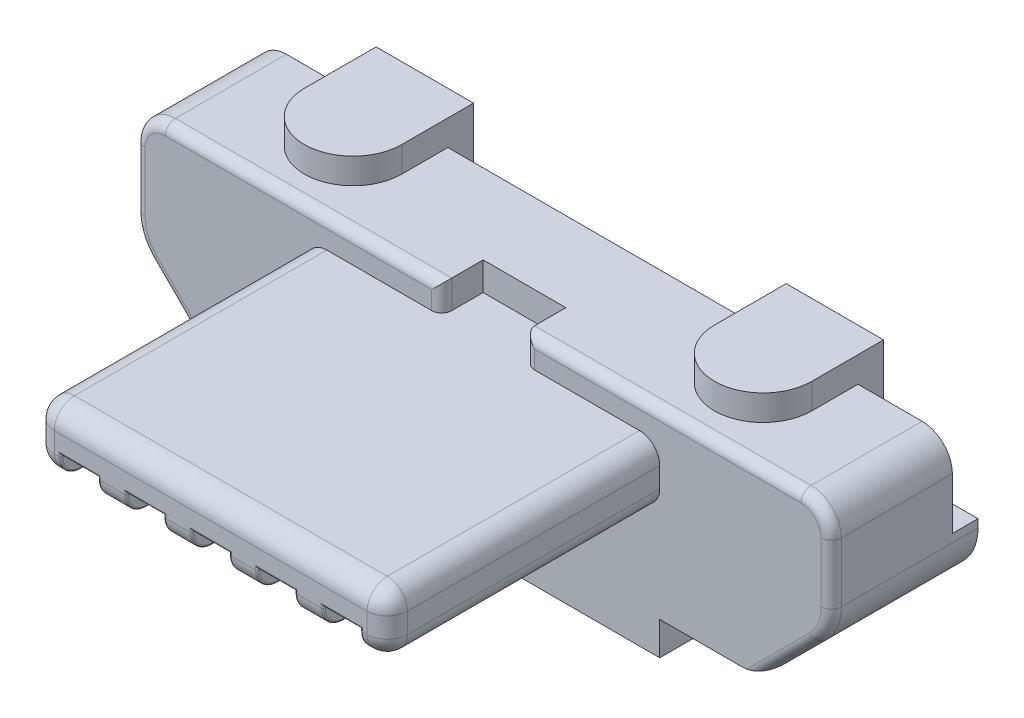
SolidWorks part; units mm, degrees
ref_plane "Front Plane" through (0, 0, 0) normal (0, 0, 1) x (1, 0, 0)
ref_plane "Top Plane" through (0, 0, 0) normal (0, 1, 0) x (1, 0, 0)
ref_plane "Right Plane" through (0, 0, 0) normal (1, 0, 0) x (0, 0, -1)
sketch "Sketch1" plane through (0, 0, 0) normal (0, 0, 1) x (1, 0, 0)
  line L0 (3.45, 0.925) -> (-3.45, 0.925)
  line L1 (-3.45, 0.925) -> (-3.45, -0.175)
  line L2 (-3.45, -0.175) -> (-2.7, -0.925)
  line L3 (-2.7, -0.925) -> (2.7, -0.925)
  line L4 (2.7, -0.925) -> (3.45, -0.175)
  line L5 (3.45, -0.175) -> (3.45, 0.925)
  line L6 (0, 0.925) -> (0, -0.925) construction
  dimension "D1" = 6.9
  dimension "D2" = 1.85
extrude "Boss-Extrude1" add sketch "Sketch1" along normal blind 1.2
fillet "Fillet1" radius 0.3 2 edges at (-3.45, 0.925, 0.6) (3.45, 0.925, 0.6)
sketch "Sketch5" plane through (0, -0.925, 0) normal (0, -1, 0) x (1, 0, 0)
  line L0 (-2.7, 1.2) -> (2.7, 1.2) construction
  line L1 (-1.75, 1.2) -> (1.75, 1.2)
  line L2 (-1.75, 1.2) -> (-1.75, 0.8)
  line L3 (-1.75, 0.8) -> (1.75, 0.8)
  line L4 (1.75, 1.2) -> (1.75, 0.8)
  line L5 (0, 0.8) -> (0, 0) construction
  dimension "D1" = 0.4
  dimension "D2" = 3.5
extrude "Boss-Extrude3" add sketch "Sketch5" along normal blind 0.28
sketch "Sketch7" plane through (-1.75, 0, 0) normal (-1, 0, 0) x (0, 0, 1)
  line L0 (0, -0.925) -> (1.2, -0.875)
  line L1 (1.2, -0.925) -> (0, -0.925)
  line L2 (1.2, -0.925) -> (1.2, -0.875)
  dimension "D1" = 0.05
extrude "Cut-Extrude3" cut sketch "Sketch7" along normal blind 2.28
sketch "Sketch8" plane through (1.75, 0, 0) normal (1, 0, 0) x (0, 0, -1)
  line L3 (0, -0.925) -> (-1.2, -0.875)
  line L4 (-1.2, -0.875) -> (-1.2, -0.925)
  line L5 (-1.2, -0.925) -> (0, -0.925)
  line L6 (0, -0.925) -> (-1.2, -0.875)
  line L7 (-1.2, -0.875) -> (-1.2, -0.925)
  line L8 (-1.2, -0.925) -> (0, -0.925)
  dimension "D1" = 0
extrude "Cut-Extrude4" cut sketch "Sketch8" along normal blind 2.28
sketch "Sketch2" plane through (0, 0, 1.2) normal (0, 0, 1) x (1, 0, 0)
  line L1 (-0.41, 1.465) -> (0.41, 1.465)
  line L2 (-0.41, 1.465) -> (-0.41, 0.645)
  line L3 (-0.41, 0.645) -> (0.41, 0.645)
  line L4 (0.41, 1.465) -> (0.41, 0.645)
  line L5 (-0.41, 1.465) -> (0.41, 0.645) construction
  line L6 (-0.41, 0.645) -> (0.41, 1.465) construction
  line L7 (3.15, 0.925) -> (-3.15, 0.925) construction
  point P0 (0, 1.055)
  dimension "D1" = 0.82
  dimension "D2" = 0.28
extrude "Cut-Extrude1" cut sketch "Sketch2" against normal blind 0.41
sketch "Sketch3" plane through (0, 0, 1.2) normal (0, 0, 1) x (1, 0, 0)
  line L1 (-1.75, 0.645) -> (1.75, 0.645)
  line L2 (-1.75, 0.645) -> (-1.75, 0.045)
  line L3 (-1.75, 0.045) -> (1.75, 0.045)
  line L4 (1.75, 0.645) -> (1.75, 0.045)
  line L5 (-1.75, 0.645) -> (1.75, 0.045) construction
  line L6 (-1.75, 0.045) -> (1.75, 0.645) construction
  line L7 (3.15, 0.925) -> (0.41, 0.925) construction
  point P0 (0, 0.345)
  dimension "D1" = 0.28
  dimension "D2" = 3.5
  dimension "D3" = 0.6
extrude "Boss-Extrude2" add sketch "Sketch3" along normal blind 2.7
fillet "Fillet5" radius 0.2 8 edges at (0, 0.045, 3.9) (-1.75, 0.345, 3.9) (0, 0.645, 3.9) (1.75, 0.345, 3.9) (-1.75, 0.045, 2.55) (-1.75, 0.645, 2.55) (1.75, 0.045, 2.55) (1.75, 0.645, 2.55)
fillet "Fillet7" radius 0.5 4 edges at (3.45, -0.175, 0.6) (2.725, -0.9, 0.6) (-2.725, -0.9, 0.6) (-3.45, -0.175, 0.6)
fillet "Fillet8" radius 0.1 12 edges at (-3.45, 0.3286, 1.2) (3.45, 0.3286, 1.2) (3.3621, 0.8371, 1.2) (-3.3621, 0.8371, 1.2) (-1.78, 0.925, 1.2) (1.78, 0.925, 1.2) (3.1002, -0.5248, 1.2) (-3.1002, -0.5248, 1.2) (3.4119, -0.1592, 1.2) (-3.4119, -0.1592, 1.2)
sketch "Sketch9" plane through (0, -0.925, 0) normal (0, -1, 0) x (1, 0, 0)
  line L0 (1.75, 0.8) -> (1.75, 0) construction
  line L1 (-1.75, 0.05) -> (1.75, 0.05)
  line L2 (-1.75, 0.05) -> (-1.75, 0.65)
  line L3 (-1.75, 0.65) -> (1.75, 0.65)
  line L4 (1.75, 0.05) -> (1.75, 0.65)
  line L5 (-1.75, 0) -> (1.75, 0) construction
  dimension "D1" = 0.05
  dimension "D2" = 0.6
extrude "Boss-Extrude4" add sketch "Sketch9" along normal blind 0.16
sketch "Sketch10" plane through (0, 0, 3.9) normal (0, 0, 1) x (1, 0, 0)
  line L0 (-1.3, 0.265) -> (-1.3, -0.105) construction
  line L1 (-1.485, 0.265) -> (-1.115, 0.265)
  line L2 (-1.485, 0.265) -> (-1.485, -0.105)
  line L3 (-1.485, -0.105) -> (-1.115, -0.105)
  line L4 (-1.115, 0.265) -> (-1.115, -0.105)
  line L5 (-0.835, 0.265) -> (-0.465, 0.265)
  line L6 (-0.835, 0.265) -> (-0.835, -0.105)
  line L7 (-0.835, -0.105) -> (-0.465, -0.105)
  line L8 (-0.465, 0.265) -> (-0.465, -0.105)
  line L9 (-0.185, 0.265) -> (0.185, 0.265)
  line L10 (-0.185, 0.265) -> (-0.185, -0.105)
  line L11 (-0.185, -0.105) -> (0.185, -0.105)
  line L12 (0.185, 0.265) -> (0.185, -0.105)
  line L13 (0.465, 0.265) -> (0.835, 0.265)
  line L14 (0.465, 0.265) -> (0.465, -0.105)
  line L15 (0.465, -0.105) -> (0.835, -0.105)
  line L16 (0.835, 0.265) -> (0.835, -0.105)
  line L17 (1.115, 0.265) -> (1.485, 0.265)
  line L18 (1.115, 0.265) -> (1.115, -0.105)
  line L19 (1.115, -0.105) -> (1.485, -0.105)
  line L20 (1.485, 0.265) -> (1.485, -0.105)
  line L21 (1.3, 0.265) -> (1.3, -0.105) construction
  line L22 (0.65, 0.265) -> (0.65, -0.105) construction
  line L23 (0, 0.265) -> (0, -0.105) construction
  line L24 (-0.65, 0.265) -> (-0.65, -0.105) construction
  line L25 (-1.55, 0.045) -> (1.55, 0.045) construction
  dimension "D1" = 0.37
  dimension "D2" = 2.6
  dimension "D3" = 0.28
  dimension "D4" = 0.28
  dimension "D5" = 0.28
  dimension "D6" = 0.28
  dimension "D7" = 0.22
extrude "Cut-Extrude5" cut sketch "Sketch10" against normal up to surface (2.7 mm away) up to face at (0.0371, 0.0086, 1.2)
ref_plane "Plane1" through (0, 0, 3.7) normal (0, 0, 1) x (1, 0, 0)
sketch "Sketch11" plane through (0, 0, 3.7) normal (0, 0, 1) x (1, 0, 0)
  line L0 (-1.485, 0.045) -> (-1.485, 0.265) construction
  line L1 (-1.485, 0.165) -> (-1.115, 0.165)
  line L2 (-1.485, 0.165) -> (-1.485, 0.315)
  line L3 (-1.485, 0.315) -> (-1.115, 0.315)
  line L4 (-1.115, 0.165) -> (-1.115, 0.315)
  line L5 (-0.51, 0.645) -> (-1.55, 0.645) construction
  line L6 (-1.115, 0.245) -> (-1.115, 0.045) construction
  line L7 (-0.835, 0.315) -> (-0.465, 0.315)
  line L8 (-0.835, 0.165) -> (-0.835, 0.315)
  line L9 (-0.835, 0.165) -> (-0.465, 0.165)
  line L10 (-0.465, 0.165) -> (-0.465, 0.315)
  line L11 (-0.185, 0.315) -> (0.185, 0.315)
  line L12 (-0.185, 0.165) -> (-0.185, 0.315)
  line L13 (-0.185, 0.165) -> (0.185, 0.165)
  line L14 (0.185, 0.165) -> (0.185, 0.315)
  line L15 (0.465, 0.315) -> (0.835, 0.315)
  line L16 (0.465, 0.165) -> (0.465, 0.315)
  line L17 (0.465, 0.165) -> (0.835, 0.165)
  line L18 (0.835, 0.165) -> (0.835, 0.315)
  line L19 (1.115, 0.315) -> (1.485, 0.315)
  line L20 (1.115, 0.165) -> (1.115, 0.315)
  line L21 (1.115, 0.165) -> (1.485, 0.165)
  line L22 (1.485, 0.165) -> (1.485, 0.315)
  dimension "D1" = 0.15
  dimension "D2" = 0.48
  dimension "D3" = 5
sketch "Sketch12" plane through (0, 0, 0) normal (1, 0, 0) x (0, 0, -1)
  line L0 (-3.7, 0.315) -> (-0.55, 0.315)
  line L1 (-3.7, 0.165) -> (-3.7, 0.315) construction
  line L2 (-3.7, 0.165) -> (-3.7, 0.315) construction
  line L3 (-0.35, 0.115) -> (-0.35, -1.085)
  line L4 (0, -0.7781) -> (0, -0.3214) construction
  line L5 (-0.05, -1.085) -> (-0.65, -1.085) construction
  arc A0 (-0.55, 0.315) -> (-0.35, 0.115) centre (-0.55, 0.115) cw
  dimension "D1" = 0.2
  dimension "D2" = 0.35
sketch "Sketch13" plane through (0, 0, 3.7) normal (0, 0, 1) x (1, 0, 0)
  line L0 (-1.485, 0.315) -> (-1.115, 0.315) construction
  line L1 (-1.425, 0.315) -> (-1.175, 0.315)
  line L2 (-1.425, 0.315) -> (-1.425, 0.165)
  line L3 (-1.425, 0.165) -> (-1.175, 0.165)
  line L4 (-1.175, 0.315) -> (-1.175, 0.165)
  line L5 (-1.485, 0.165) -> (-1.115, 0.165) construction
  line L6 (-1.485, 0.045) -> (-1.175, 0.315) construction
  line L7 (-1.175, 0.315) -> (-1.1728, 0.3168) construction
  line L8 (-1.115, 0.045) -> (-1.425, 0.315) construction
  line L12 (-0.775, 0.315) -> (-0.525, 0.315)
  line L13 (-0.775, 0.315) -> (-0.775, 0.165)
  line L14 (-0.775, 0.165) -> (-0.525, 0.165)
  line L15 (-0.525, 0.315) -> (-0.525, 0.165)
  line L16 (-0.125, 0.315) -> (0.125, 0.315)
  line L17 (-0.125, 0.315) -> (-0.125, 0.165)
  line L18 (-0.125, 0.165) -> (0.125, 0.165)
  line L19 (0.125, 0.315) -> (0.125, 0.165)
  line L20 (0.525, 0.315) -> (0.775, 0.315)
  line L21 (0.525, 0.315) -> (0.525, 0.165)
  line L22 (0.525, 0.165) -> (0.775, 0.165)
  line L23 (0.775, 0.315) -> (0.775, 0.165)
  line L24 (1.175, 0.315) -> (1.425, 0.315)
  line L25 (1.175, 0.315) -> (1.175, 0.165)
  line L26 (1.175, 0.165) -> (1.425, 0.165)
  line L27 (1.425, 0.315) -> (1.425, 0.165)
  dimension "D1" = 0.25
  dimension "D2" = 5
sweep "Cut-Sweep2" cut profiles "Sketch13" path "Sketch12"
extrude "Cut-Extrude6" cut sketch "Sketch11" against normal blind 2.8
sketch "Sketch14" plane through (0, 0, 3.7) normal (0, 0, 1) x (1, 0, 0)
  line L4 (-1.175, 0.315) -> (-1.425, 0.315)
  line L5 (-1.175, 0.165) -> (-1.175, 0.315)
  line L6 (-1.425, 0.165) -> (-1.175, 0.165)
  line L7 (-1.425, 0.315) -> (-1.425, 0.165)
  line L8 (-1.175, 0.315) -> (-1.425, 0.315)
  line L9 (-1.175, 0.165) -> (-1.175, 0.315)
  line L10 (-1.425, 0.165) -> (-1.175, 0.165)
  line L11 (-1.425, 0.315) -> (-1.425, 0.165)
  line L12 (1.425, 0.315) -> (1.175, 0.315)
  line L13 (1.425, 0.165) -> (1.425, 0.315)
  line L14 (1.175, 0.165) -> (1.425, 0.165)
  line L15 (1.175, 0.315) -> (1.175, 0.165)
  line L16 (1.425, 0.315) -> (1.175, 0.315)
  line L17 (1.425, 0.165) -> (1.425, 0.315)
  line L18 (1.175, 0.165) -> (1.425, 0.165)
  line L19 (1.175, 0.315) -> (1.175, 0.165)
  line L20 (0.775, 0.315) -> (0.525, 0.315)
  line L21 (0.775, 0.165) -> (0.775, 0.315)
  line L22 (0.525, 0.165) -> (0.775, 0.165)
  line L23 (0.525, 0.315) -> (0.525, 0.165)
  line L24 (0.775, 0.315) -> (0.525, 0.315)
  line L25 (0.775, 0.165) -> (0.775, 0.315)
  line L26 (0.525, 0.165) -> (0.775, 0.165)
  line L27 (0.525, 0.315) -> (0.525, 0.165)
  line L28 (0.125, 0.315) -> (-0.125, 0.315)
  line L29 (0.125, 0.165) -> (0.125, 0.315)
  line L30 (-0.125, 0.165) -> (0.125, 0.165)
  line L31 (-0.125, 0.315) -> (-0.125, 0.165)
  line L32 (0.125, 0.315) -> (-0.125, 0.315)
  line L33 (0.125, 0.165) -> (0.125, 0.315)
  line L34 (-0.125, 0.165) -> (0.125, 0.165)
  line L35 (-0.125, 0.315) -> (-0.125, 0.165)
  line L36 (-0.525, 0.315) -> (-0.775, 0.315)
  line L37 (-0.775, 0.315) -> (-0.775, 0.165)
  line L38 (-0.775, 0.165) -> (-0.525, 0.165)
  line L39 (-0.525, 0.165) -> (-0.525, 0.315)
  line L40 (-0.525, 0.315) -> (-0.775, 0.315)
  line L41 (-0.775, 0.315) -> (-0.775, 0.165)
  line L42 (-0.775, 0.165) -> (-0.525, 0.165)
  line L43 (-0.525, 0.165) -> (-0.525, 0.315)
  dimension "D1" = 0
  dimension "D2" = 0
  dimension "D3" = 0
  dimension "D4" = 0
  dimension "D5" = 0
sketch "Sketch15" plane through (0, 0, 0) normal (1, 0, 0) x (0, 0, -1)
  line L1 (0, -0.7781) -> (0, -0.3214) construction
  line L4 (-0.35, 0.115) -> (-0.35, -1.085) construction
  line L5 (-3.7, 0.315) -> (-0.55, 0.315) construction
  line L6 (-0.35, 0.115) -> (-0.35, -1.035)
  line L7 (-0.3, -1.085) -> (0.889, -1.085)
  line L9 (-0.05, -1.085) -> (-0.65, -1.085) construction
  line L10 (-3.7, 0.315) -> (-0.55, 0.315)
  arc A2 (-0.35, 0.115) -> (-0.55, 0.315) centre (-0.55, 0.115) ccw construction
  arc A4 (-0.35, -1.035) -> (-0.3, -1.085) centre (-0.3, -1.035) ccw
  arc A5 (-0.35, 0.115) -> (-0.55, 0.315) centre (-0.55, 0.115) ccw
  dimension "D1" = 0.889
  dimension "D2" = 0.05
sweep "Sweep3" add profiles "Sketch14" path "Sketch15"
sketch "Sketch16" plane through (0, -1.085, 0) normal (0, -1, 0) x (1, 0, 0)
  line L0 (1.75, 0.65) -> (-1.75, 0.65) construction
  line L1 (-1.175, 0.5) -> (-1.425, 0.5)
  line L2 (-1.175, 0.5) -> (-1.175, 0.65)
  line L3 (-1.175, 0.65) -> (-1.425, 0.65)
  line L4 (-1.425, 0.5) -> (-1.425, 0.65)
  line L5 (-1.425, 0.5) -> (-1.425, 0.3) construction
  line L6 (-0.775, 0.5) -> (-0.775, 0.65)
  line L7 (-0.525, 0.65) -> (-0.775, 0.65)
  line L8 (-0.525, 0.5) -> (-0.525, 0.65)
  line L9 (-0.525, 0.5) -> (-0.775, 0.5)
  line L10 (-0.125, 0.5) -> (-0.125, 0.65)
  line L11 (0.125, 0.65) -> (-0.125, 0.65)
  line L12 (0.125, 0.5) -> (0.125, 0.65)
  line L13 (0.125, 0.5) -> (-0.125, 0.5)
  line L14 (0.525, 0.5) -> (0.525, 0.65)
  line L15 (0.775, 0.65) -> (0.525, 0.65)
  line L16 (0.775, 0.5) -> (0.775, 0.65)
  line L17 (0.775, 0.5) -> (0.525, 0.5)
  line L18 (1.175, 0.5) -> (1.175, 0.65)
  line L19 (1.425, 0.65) -> (1.175, 0.65)
  line L20 (1.425, 0.5) -> (1.425, 0.65)
  line L21 (1.425, 0.5) -> (1.175, 0.5)
  dimension "D1" = 5
extrude "Cut-Extrude7" cut sketch "Sketch16" against normal up to surface (0.16 mm away) up to face at (0, -0.925, 0.725)
sketch "Sketch17" plane through (0, 0, 3.7) normal (0, 0, 1) x (1, 0, 0)
  line L4 (-0.465, 0.315) -> (-0.835, 0.315)
  line L5 (-0.465, 0.165) -> (-0.465, 0.315)
  line L6 (-0.835, 0.165) -> (-0.465, 0.165)
  line L7 (-0.835, 0.315) -> (-0.835, 0.165)
  line L8 (-0.465, 0.315) -> (-0.835, 0.315)
  line L9 (-0.465, 0.165) -> (-0.465, 0.315)
  line L10 (-0.835, 0.165) -> (-0.465, 0.165)
  line L11 (-0.835, 0.315) -> (-0.835, 0.165)
  line L12 (-1.485, 0.165) -> (-1.115, 0.165)
  line L13 (-1.115, 0.165) -> (-1.115, 0.315)
  line L14 (-1.115, 0.315) -> (-1.485, 0.315)
  line L15 (-1.485, 0.315) -> (-1.485, 0.165)
  line L16 (-1.485, 0.165) -> (-1.115, 0.165)
  line L17 (-1.115, 0.165) -> (-1.115, 0.315)
  line L18 (-1.115, 0.315) -> (-1.485, 0.315)
  line L19 (-1.485, 0.315) -> (-1.485, 0.165)
  line L20 (1.485, 0.315) -> (1.115, 0.315)
  line L21 (1.485, 0.165) -> (1.485, 0.315)
  line L22 (1.115, 0.165) -> (1.485, 0.165)
  line L23 (1.115, 0.315) -> (1.115, 0.165)
  line L24 (1.485, 0.315) -> (1.115, 0.315)
  line L25 (1.485, 0.165) -> (1.485, 0.315)
  line L26 (1.115, 0.165) -> (1.485, 0.165)
  line L27 (1.115, 0.315) -> (1.115, 0.165)
  line L28 (0.835, 0.315) -> (0.465, 0.315)
  line L29 (0.835, 0.165) -> (0.835, 0.315)
  line L30 (0.465, 0.165) -> (0.835, 0.165)
  line L31 (0.465, 0.315) -> (0.465, 0.165)
  line L32 (0.835, 0.315) -> (0.465, 0.315)
  line L33 (0.835, 0.165) -> (0.835, 0.315)
  line L34 (0.465, 0.165) -> (0.835, 0.165)
  line L35 (0.465, 0.315) -> (0.465, 0.165)
  line L36 (0.185, 0.315) -> (-0.185, 0.315)
  line L37 (0.185, 0.165) -> (0.185, 0.315)
  line L38 (-0.185, 0.165) -> (0.185, 0.165)
  line L39 (-0.185, 0.315) -> (-0.185, 0.165)
  line L40 (0.185, 0.315) -> (-0.185, 0.315)
  line L41 (0.185, 0.165) -> (0.185, 0.315)
  line L42 (-0.185, 0.165) -> (0.185, 0.165)
  line L43 (-0.185, 0.315) -> (-0.185, 0.165)
  dimension "D1" = 0
  dimension "D2" = 0
  dimension "D3" = 0
  dimension "D4" = 0
  dimension "D5" = 0
extrude "Boss-Extrude5" add sketch "Sketch17" against normal blind 2.8
sketch "Sketch18" plane through (0, 0.315, 0) normal (0, -1, 0) x (1, 0, 0)
  line L0 (0.11, 3.7) -> (-0.11, 3.7) construction
  line L1 (1.115, 3.7) -> (1.485, 3.7)
  line L2 (1.115, 3.7) -> (1.115, 3.55)
  line L3 (1.115, 3.55) -> (1.485, 3.55)
  line L4 (1.485, 3.7) -> (1.485, 3.55)
  line L5 (1.115, 1.2) -> (1.115, 3.7) construction
  line L6 (1.485, 3.7) -> (1.485, 1.2) construction
  line L7 (0.465, 3.7) -> (0.835, 3.7)
  line L8 (0.465, 3.55) -> (0.835, 3.55)
  line L9 (0.465, 3.7) -> (0.465, 3.55)
  line L10 (0.835, 3.7) -> (0.835, 3.55)
  line L11 (-0.185, 3.7) -> (0.185, 3.7)
  line L12 (-0.185, 3.55) -> (0.185, 3.55)
  line L13 (-0.185, 3.7) -> (-0.185, 3.55)
  line L14 (0.185, 3.7) -> (0.185, 3.55)
  line L15 (-0.835, 3.7) -> (-0.465, 3.7)
  line L16 (-0.835, 3.55) -> (-0.465, 3.55)
  line L17 (-0.835, 3.7) -> (-0.835, 3.55)
  line L18 (-0.465, 3.7) -> (-0.465, 3.55)
  line L19 (-1.485, 3.7) -> (-1.115, 3.7)
  line L20 (-1.485, 3.55) -> (-1.115, 3.55)
  line L21 (-1.485, 3.7) -> (-1.485, 3.55)
  line L22 (-1.115, 3.7) -> (-1.115, 3.55)
  line L23 (-1.485, 0.9) -> (-1.485, 3.7) construction
  dimension "D1" = 0.15
  dimension "D2" = 5
extrude "Cut-Extrude8" cut sketch "Sketch18" against normal blind 0.15
fillet "Fillet10" radius 0.1 10 edges at (1.3, 0.315, 3.55) (0.65, 0.315, 3.55) (0, 0.315, 3.55) (-0.65, 0.315, 3.55) (-1.3, 0.315, 3.55) (-1.3, -1.085, 0.35) (-0.65, -1.085, 0.35) (0, -1.085, 0.35) (0.65, -1.085, 0.35) (1.3, -1.085, 0.35)
sketch "Sketch19" plane through (0, 0.315, 0) normal (0, 1, 0) x (1, 0, 0)
  line L0 (-0.11, -3.7) -> (0.11, -3.7) construction
  line L1 (-1.485, -3.7) -> (-1.115, -3.7)
  line L2 (-1.485, -3.7) -> (-1.485, -3.55)
  line L3 (-1.485, -3.55) -> (-1.115, -3.55)
  line L4 (-1.115, -3.7) -> (-1.115, -3.55)
  line L5 (-1.115, -0.9) -> (-1.115, -3.7) construction
  line L6 (-1.485, -0.9) -> (-1.485, -3.7) construction
  line L7 (-0.835, -3.7) -> (-0.835, -3.55)
  line L8 (-0.835, -3.55) -> (-0.465, -3.55)
  line L9 (-0.835, -3.7) -> (-0.465, -3.7)
  line L10 (-0.465, -3.7) -> (-0.465, -3.55)
  line L11 (-0.185, -3.7) -> (-0.185, -3.55)
  line L12 (-0.185, -3.55) -> (0.185, -3.55)
  line L13 (-0.185, -3.7) -> (0.185, -3.7)
  line L14 (0.185, -3.7) -> (0.185, -3.55)
  line L15 (0.465, -3.7) -> (0.465, -3.55)
  line L16 (0.465, -3.55) -> (0.835, -3.55)
  line L17 (0.465, -3.7) -> (0.835, -3.7)
  line L18 (0.835, -3.7) -> (0.835, -3.55)
  line L19 (1.115, -3.7) -> (1.115, -3.55)
  line L20 (1.115, -3.55) -> (1.485, -3.55)
  line L21 (1.115, -3.7) -> (1.485, -3.7)
  line L22 (1.485, -3.7) -> (1.485, -3.55)
  dimension "D1" = 0.15
extrude "Boss-Extrude6" add sketch "Sketch19" along normal blind 0.15
fillet "Fillet11" radius 0.15 1 edges at (1.3, 0.165, 3.7)
fillet "Fillet12" radius 0.15 1 edges at (0.65, 0.165, 3.7)
fillet "Fillet13" radius 0.15 1 edges at (0, 0.165, 3.7)
fillet "Fillet14" radius 0.15 1 edges at (-0.65, 0.165, 3.7)
fillet "Fillet15" radius 0.15 1 edges at (-1.3, 0.165, 3.7)
fillet "Fillet16" radius 0.01 11 edges at (-1.425, 0.1504, 0.5146) (-1.175, 0.1504, 0.5146) (-1.425, -0.46, 0.5) (-1.175, -0.46, 0.5) (-1.425, -1.1764, 0.4414) (-1.175, -1.1764, 0.4414) (-1.3, -1.235, -0.889) (-1.425, -1.235, -0.2945) (-1.175, -1.235, -0.2945) (-1.175, 0.165, 0.725) (-1.425, 0.165, 0.725)
fillet "Fillet17" radius 0.01 11 edges at (-0.775, 0.1504, 0.5146) (-0.525, 0.1504, 0.5146) (-0.775, -0.46, 0.5) (-0.525, -0.46, 0.5) (-0.775, -1.1764, 0.4414) (-0.525, -1.1764, 0.4414) (-0.65, -1.235, -0.889) (-0.775, -1.235, -0.2945) (-0.525, -1.235, -0.2945) (-0.525, 0.165, 0.725) (-0.775, 0.165, 0.725)
fillet "Fillet18" radius 0.01 11 edges at (-0.125, 0.1504, 0.5146) (0.125, 0.1504, 0.5146) (-0.125, -0.46, 0.5) (0.125, -0.46, 0.5) (-0.125, -1.1764, 0.4414) (0.125, -1.1764, 0.4414) (0, -1.235, -0.889) (-0.125, -1.235, -0.2945) (0.125, -1.235, -0.2945) (0.125, 0.165, 0.725) (-0.125, 0.165, 0.725)
fillet "Fillet19" radius 0.01 11 edges at (0.525, 0.1504, 0.5146) (0.775, 0.1504, 0.5146) (0.525, -0.46, 0.5) (0.775, -0.46, 0.5) (0.525, -1.1764, 0.4414) (0.775, -1.1764, 0.4414) (0.65, -1.235, -0.889) (0.525, -1.235, -0.2945) (0.775, -1.235, -0.2945) (0.775, 0.165, 0.725) (0.525, 0.165, 0.725)
fillet "Fillet20" radius 0.01 11 edges at (1.175, 0.1504, 0.5146) (1.425, 0.1504, 0.5146) (1.175, -0.46, 0.5) (1.425, -0.46, 0.5) (1.175, -1.1764, 0.4414) (1.425, -1.1764, 0.4414) (1.3, -1.235, -0.889) (1.175, -1.235, -0.2945) (1.425, -1.235, -0.2945) (1.425, 0.165, 0.725) (1.175, 0.165, 0.725)
fillet "Fillet21" radius 0.01 11 edges at (1.425, 0.315, 0.725) (1.175, 0.315, 0.725) (1.425, 0.2564, 0.4086) (1.175, 0.2564, 0.4086) (1.425, -0.46, 0.35) (1.175, -0.46, 0.35) (1.425, -1.0704, 0.3354) (1.175, -1.0704, 0.3354) (1.425, -1.085, -0.2945) (1.175, -1.085, -0.2945) (1.3, -1.085, -0.889)
fillet "Fillet22" radius 0.01 11 edges at (0.775, 0.315, 0.725) (0.525, 0.315, 0.725) (0.775, 0.2564, 0.4086) (0.525, 0.2564, 0.4086) (0.775, -0.46, 0.35) (0.525, -0.46, 0.35) (0.775, -1.0704, 0.3354) (0.525, -1.0704, 0.3354) (0.775, -1.085, -0.2945) (0.525, -1.085, -0.2945) (0.65, -1.085, -0.889)
fillet "Fillet23" radius 0.01 11 edges at (0.125, 0.315, 0.725) (-0.125, 0.315, 0.725) (0.125, 0.2564, 0.4086) (-0.125, 0.2564, 0.4086) (0.125, -0.46, 0.35) (-0.125, -0.46, 0.35) (0.125, -1.0704, 0.3354) (-0.125, -1.0704, 0.3354) (0.125, -1.085, -0.2945) (-0.125, -1.085, -0.2945) (0, -1.085, -0.889)
fillet "Fillet24" radius 0.01 11 edges at (-0.525, 0.315, 0.725) (-0.775, 0.315, 0.725) (-0.525, 0.2564, 0.4086) (-0.775, 0.2564, 0.4086) (-0.525, -0.46, 0.35) (-0.775, -0.46, 0.35) (-0.525, -1.0704, 0.3354) (-0.775, -1.0704, 0.3354) (-0.525, -1.085, -0.2945) (-0.775, -1.085, -0.2945) (-0.65, -1.085, -0.889)
fillet "Fillet25" radius 0.01 11 edges at (-1.175, 0.315, 0.725) (-1.425, 0.315, 0.725) (-1.175, 0.2564, 0.4086) (-1.425, 0.2564, 0.4086) (-1.175, -0.46, 0.35) (-1.425, -0.46, 0.35) (-1.175, -1.0704, 0.3354) (-1.425, -1.0704, 0.3354) (-1.175, -1.085, -0.2945) (-1.425, -1.085, -0.2945) (-1.3, -1.085, -0.889)
fillet "Fillet26" radius 0.02 35 edges at (1.115, 0.255, 3.9) (1.115, 0.045, 2.45) (-1.115, 0.045, 2.45) (-1.115, 0.255, 3.9) (-0.465, 0.045, 2.45) (-0.465, 0.255, 3.9) (0.185, 0.045, 2.45) (0.185, 0.255, 3.9) (0.835, 0.045, 2.45) (0.835, 0.255, 3.9) (1.485, 0.045, 2.45) (1.485, 0.255, 3.9) (-1.485, 0.255, 3.9) (-1.485, 0.045, 2.45) (-0.835, 0.255, 3.9) (-0.835, 0.045, 2.45) (-0.185, 0.255, 3.9) (-0.185, 0.045, 2.45) (0.465, 0.255, 3.9) (0.465, 0.045, 2.45) (1.115, 0.1036, 3.8414) (-1.115, 0.1036, 3.8414) (-0.465, 0.1036, 3.8414) (0.185, 0.1036, 3.8414) (0.835, 0.1036, 3.8414) (1.485, 0.1036, 3.8414) (-1.485, 0.1036, 3.8414) (-0.835, 0.1036, 3.8414) (-0.185, 0.1036, 3.8414) (0.465, 0.1036, 3.8414) (-1.3, 0.265, 3.9) (-0.65, 0.265, 3.9) (0, 0.265, 3.9) (0.65, 0.265, 3.9) (1.3, 0.265, 3.9)
sketch "Sketch20" plane through (0, 0, 0) normal (0, 0, -1) x (-1, 0, 0)
  line L0 (-3.15, 0.925) -> (3.15, 0.925) construction
  line L1 (1.5494, 0.925) -> (2.5146, 0.925)
  line L2 (1.5494, 0.925) -> (1.5494, -0.9245)
  line L3 (1.5494, -0.9245) -> (2.5146, -0.9245)
  line L4 (2.5146, 0.925) -> (2.5146, 0.1122)
  line L5 (2.5146, -0.599) -> (2.5146, -0.9245)
  line L6 (2.5146, 0.1122) -> (3.026, 0.1122)
  line L7 (2.032, 0.925) -> (2.032, -0.9245) construction
  line L8 (2.5146, -0.599) -> (3.026, -0.599)
  line L9 (3.026, 0.1122) -> (3.026, -0.599) construction
  line L10 (3.3036, -0.3214) -> (2.8469, -0.7781) construction
  line L11 (3.026, 0.1122) -> (3.45, 0.1122)
  line L12 (3.45, 0.625) -> (3.45, 0.0321) construction
  line L13 (3.45, 0.1122) -> (3.45, 0.0321)
  line L14 (3.3036, -0.3214) -> (3.026, -0.599)
  arc A0 (3.45, 0.0321) -> (3.3036, -0.3214) centre (2.95, 0.0321) cw
  arc A1 (3.3036, -0.3214) -> (3.45, 0.0321) centre (2.95, 0.0321) ccw construction
  ellipse E0 centre (2.4933, -0.4246) end of major axis (2.8475, -0.0704) minor radius 0.5 (2.4925, -0.925) -> (2.8469, -0.7781) ccw construction
  point P12 (2.032, -0.9245)
  dimension "D1" = 2.032
  dimension "D2" = 0.9652
  dimension "D3" = 1.524
  dimension "D4" = 0.8128
extrude "Boss-Extrude7" add sketch "Sketch20" along normal blind 0.254
sketch "Sketch21" plane through (0, 0.925, 0) normal (0, 1, 0) x (1, 0, 0)
  line L0 (-2.5146, 0.254) -> (-2.5146, 0) construction
  line L1 (-1.5494, 0.254) -> (-2.5146, 0.254)
  line L2 (-1.5494, 0.254) -> (-1.5494, -0.4572)
  line L3 (-1.5494, -0.4572) -> (-2.5146, -0.4572) construction
  line L4 (-2.5146, 0.254) -> (-2.5146, -0.4572)
  arc A0 (-1.5494, -0.4572) -> (-2.5146, -0.4572) centre (-2.032, -0.4572) cw
  dimension "D1" = 0.7112
extrude "Boss-Extrude8" add sketch "Sketch21" along normal blind 0.254
mirror "Mirror1" about plane through (0, 0, 0) normal (1, 0, 0) of "Boss-Extrude8", "Boss-Extrude7"
